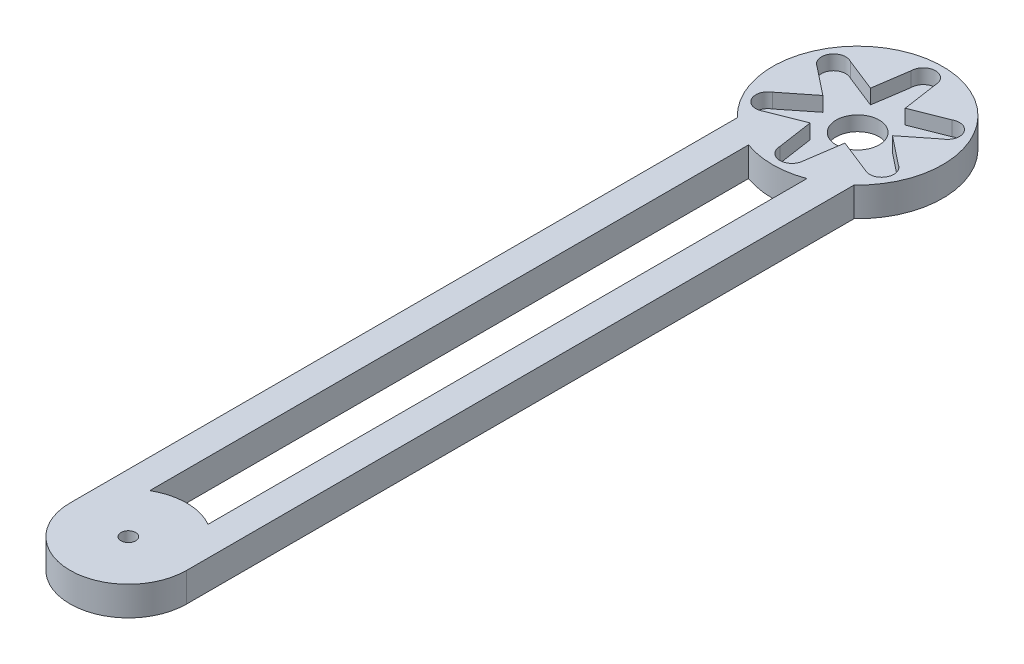
SolidWorks part; units mm, degrees
ref_plane "Front Plane" through (0, 0, 0) normal (0, 0, 1) x (1, 0, 0)
ref_plane "Top Plane" through (0, 0, 0) normal (0, 1, 0) x (1, 0, 0)
ref_plane "Right Plane" through (0, 0, 0) normal (1, 0, 0) x (0, 0, -1)
sketch "Sketch1" plane through (0, 0, 0) normal (0, 1, 0) x (1, 0, 0)
  line L0 (0, 0) -> (0, 16)
  line L2 (0, 13.5) -> (-2.5, 13.5)
  line L3 (0, 13.5) -> (2.5, 13.5)
  line L4 (-2.5, 13.5) -> (-4.5, 0)
  line L5 (2.5, 13.5) -> (4.5, 0)
  line L6 (0, 0) -> (13.8564, 8)
  line L8 (11.6913, 6.75) -> (10.4413, 8.9151)
  line L9 (11.6913, 6.75) -> (12.9413, 4.5849)
  line L10 (10.4413, 8.9151) -> (-2.25, 3.8971)
  line L11 (12.9413, 4.5849) -> (2.25, -3.8971)
  line L12 (0, 0) -> (13.8564, -8)
  line L14 (11.6913, -6.75) -> (12.9413, -4.5849)
  line L15 (11.6913, -6.75) -> (10.4413, -8.9151)
  line L16 (12.9413, -4.5849) -> (2.25, 3.8971)
  line L17 (10.4413, -8.9151) -> (-2.25, -3.8971)
  line L18 (0, 0) -> (0, -16)
  line L20 (0, -13.5) -> (2.5, -13.5)
  line L21 (0, -13.5) -> (-2.5, -13.5)
  line L22 (2.5, -13.5) -> (4.5, 0)
  line L23 (-2.5, -13.5) -> (-4.5, 0)
  line L24 (0, 0) -> (-13.8564, -8)
  line L26 (-11.6913, -6.75) -> (-10.4413, -8.9151)
  line L27 (-11.6913, -6.75) -> (-12.9413, -4.5849)
  line L28 (-10.4413, -8.9151) -> (2.25, -3.8971)
  line L29 (-12.9413, -4.5849) -> (-2.25, 3.8971)
  line L30 (0, 0) -> (-13.8564, 8)
  line L32 (-11.6913, 6.75) -> (-12.9413, 4.5849)
  line L33 (-11.6913, 6.75) -> (-10.4413, 8.9151)
  line L34 (-12.9413, 4.5849) -> (-2.25, -3.8971)
  line L35 (-10.4413, 8.9151) -> (2.25, 3.8971)
  circle A1 centre (0, 13.5) radius 2.5
  circle A3 centre (11.6913, 6.75) radius 2.5
  circle A5 centre (11.6913, -6.75) radius 2.5
  circle A7 centre (0, -13.5) radius 2.5
  circle A9 centre (-11.6913, -6.75) radius 2.5
  circle A10 centre (0, 0) radius 4.425
  circle A11 centre (-11.6913, 6.75) radius 2.5
  circle A12 centre (0, 0) radius 17.5
  point P53 (0, 0)
  dimension "D1" = 8.85
  dimension "D7" = 35
  dimension "D2" = 16
  dimension "D3" = 2.5
  dimension "D4" = 2.5
  dimension "D5" = 2.5
  dimension "D6" = 6
extrude "Boss-Extrude3" add sketch "Sketch1" along normal blind 6 contours A12 A11 L35 L4 A1 L5 L10 A3 L11 L16 A5 L17 L22 A7 L23 L28 A9 L29 L34 region at (-17.005, 0, 0)
extrude "Boss-Extrude5" add sketch "Sketch1<11>" along normal blind 3 contours L33 A11 L30 | L30 A11 L32 | L32 A11 L30 | L30 A11 L33 | A11 L30 L4 L35 | A11 L34 L29 L30 | L35 L4 L29 L10 | A10 L30 L4 L23 L24 | A10 L0 L10 L29 L30 | L29 L34 L23 L4 | A9 L24 L34 L29 | L24 A9 L27 | L27 A9 L24 | L24 A9 L26 | L26 A9 L24 | A9 L28 L23 L24 | A10 L24 L34 L17 L18 | L34 L23 L28 L17 | A7 L18 L28 L23 | A7 L22 L17 L18 | A10 L18 L28 L11 L12 | L28 L17 L22 L11 | L18 A7 L21 | L20 A7 L18 | L21 A7 L18 | L18 A7 L20 | A5 L12 L22 L17 | L15 A5 L12 | L14 A5 L12 | L12 A5 L15 | L12 A5 L14 | A5 L16 L11 L12 | A10 L12 L22 L5 L6 | L22 L11 L16 L5 | A3 L6 L16 L11 | A10 L6 L16 L35 L0 | L10 L35 L16 L5 | A3 L10 L5 L6 | L8 A3 L6 | L6 A3 L9 | L9 A3 L6 | L6 A3 L8 | A1 L0 L10 L5 | A1 L4 L35 L0 | L0 A1 L2 | L2 A1 L0 | L0 A1 L3 | L3 A1 L0 | A5 region at (-1.061, 0, -14.561) region at (1.061, 0, -12.439) region at (-1.061, 0, -12.439) region at (1.061, 0, -14.561) region at (1.6102, 0, -8.4409) region at (-1.6102, 0, -8.4409) region at (1.1071, 0, -4.2965) region at (-0.0488, 0, -4.6059) region at (-2.6346, 0, -4.5633) region at (2.6346, 0, -4.5633) region at (-6.5049, 0, -5.6149) region at (6.5049, 0, -5.6149) region at (-4.013, 0, -2.2611) region at (-5.2692, 0, 0) region at (-8.1151, 0, -2.826) region at (-10.2419, 0, -7.1384) region at (-12.0797, 0, -8.1994) region at (5.2692, 0, 0) region at (4.2749, 0, -1.1896) region at (8.1151, 0, -2.826) region at (12.0797, 0, -8.1994) region at (10.2419, 0, -7.1384) region at (-8.1151, 0, 2.826) region at (-11.303, 0, -5.3006) region at (-13.1407, 0, -6.3616) region at (11.303, 0, -5.3006) region at (8.1151, 0, 2.826) region at (13.1407, 0, -6.3616) region at (3.9644, 0, 2.3452) region at (-0.0488, 0, 4.6059) region at (-2.6346, 0, 4.5633) region at (-6.5049, 0, 5.6149) region at (-11.303, 0, 5.3006) region at (-13.1407, 0, 6.3616) region at (2.6346, 0, 4.5633) region at (6.5049, 0, 5.6149) region at (13.1407, 0, 6.3616) region at (11.303, 0, 5.3006) region at (1.6102, 0, 8.4409) region at (-1.6102, 0, 8.4409) region at (-10.2419, 0, 7.1384) region at (-12.0797, 0, 8.1994) region at (10.2419, 0, 7.1384) region at (12.0797, 0, 8.1994) region at (1.061, 0, 12.439) region at (-1.061, 0, 12.439) region at (-1.061, 0, 14.561) region at (1.061, 0, 14.561)
sketch "Sketch1<11>" plane through (0, 0, 0) normal (0, 1, 0) x (1, 0, 0) same geometry as "Sketch1"
sketch "Sketch2" plane through (0, 0, 0) normal (0, -1, 0) x (1, 0, 0)
  line L0 (-17.5, 0) -> (17.5, 0)
  line L2 (-12, 0) -> (-6, 0)
  line L3 (-12, 0) -> (-12, 150)
  line L4 (-12, 150) -> (-6, 150)
  line L5 (-6, 0) -> (-6, 150)
  line L6 (6, 0) -> (12, 0)
  line L7 (6, 0) -> (6, 150)
  line L8 (6, 150) -> (12, 150)
  line L9 (12, 0) -> (12, 150)
  circle A0 centre (0, 0) radius 17.5 construction
  circle A1 centre (0, 150) radius 12
  circle A2 centre (0, 150) radius 1.5
  circle M6 centre (0, 0) radius 17.5
  dimension "D7" = 24
  dimension "D9" = 3
  dimension "D1" = 150
  dimension "D2" = 150
  dimension "D3" = 6
  dimension "D4" = 6
  dimension "D5" = 6
  dimension "D6" = 6
  dimension "D8" = 6
extrude "Boss-Extrude6" add sketch "Sketch2" against normal blind 6 contours A1 L7 L9 M6 | A1 L3 L5 M6 | L8 A1 L4 L5 L7 A2 | L7 A1 L8 | L4 A1 L5 region at (-9.0455, 0, 78.7677) region at (9.0455, 0, 78.7677) region at (0, 0, 161.6606) region at (-8.4602, 0, 145.9296) region at (8.4602, 0, 145.9296)
